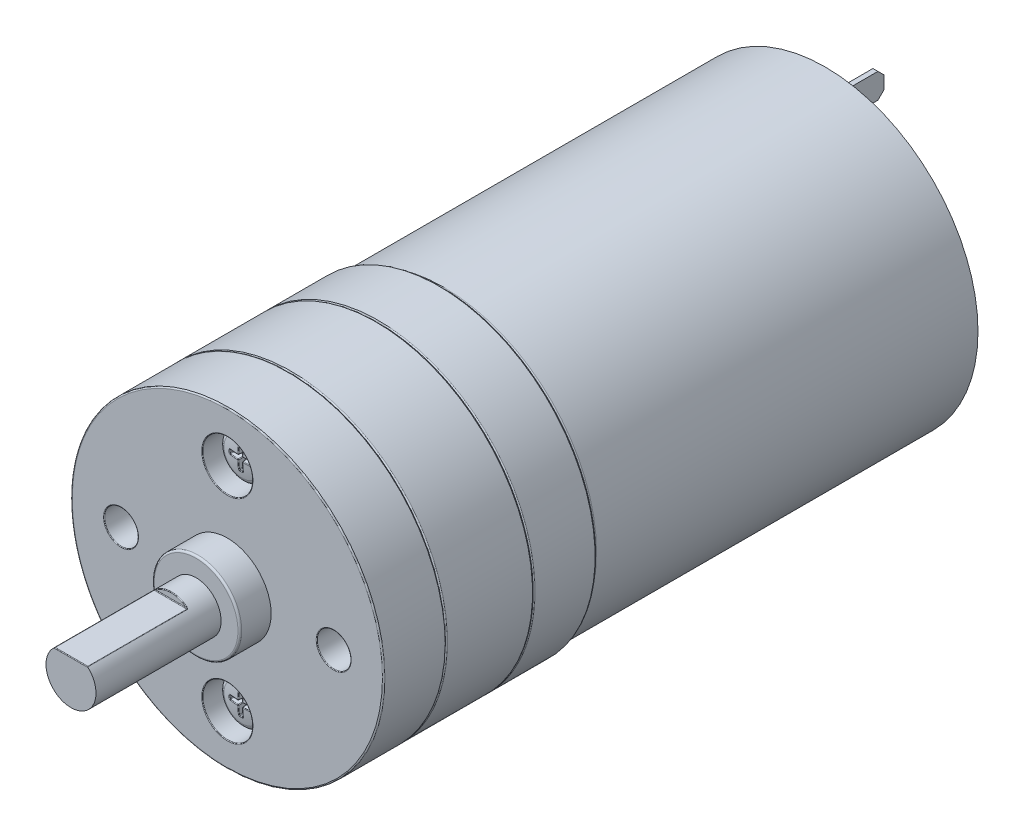
SolidWorks part; units mm, degrees
note: The reader was unsure of these and kept them because the rebuilt part matched: shared geometry of "Sketch8<3>".
material "Pololu 25D"
ref_plane "Front Plane" through (0, 0, 0) normal (0, 0, 1) x (1, 0, 0)
ref_plane "Top Plane" through (0, 0, 0) normal (0, 1, 0) x (1, 0, 0)
ref_plane "Right Plane" through (0, 0, 0) normal (1, 0, 0) x (0, 0, -1)
sketch "Sketch1" plane through (0, 0, 0) normal (0, 0, 1) x (1, 0, 0)
  line L0 (0, 14.2614) -> (0, -13.956) construction
  line L1 (-19.3981, 0) -> (18.454, 0) construction
  circle A0 centre (0, 0) radius 12.5
  dimension "D1" = 25
extrude "Boss-Extrude1" add sketch "Sketch1" along normal blind 5
fillet "Fillet1" radius 0.1 2 edges at (12.5, 0, 0) (12.5, 0, 5)
sketch "Sketch2" plane through (0, 0, 0) normal (0, 0, -1) x (-1, 0, 0)
  circle A0 centre (0, 0) radius 12.5 construction
  circle A1 centre (0, 0) radius 12.5
extrude "Boss-Extrude2" add sketch "Sketch2" along normal blind 7
fillet "Fillet2" radius 0.1 2 edges at (-12.5, 0, -7) (-12.5, 0, 0)
sketch "Sketch3" plane through (0, 0, -7) normal (0, 0, -1) x (-1, 0, 0)
  circle A0 centre (0, 0) radius 12.5 construction
  circle A1 centre (0, 0) radius 12.5
extrude "Boss-Extrude3" add sketch "Sketch3" along normal blind 5
fillet "Fillet3" radius 0.1 2 edges at (-12.5, 0, -7) (-12.5, 0, -12)
ref_plane "Plane1" through (0, 0, -12.01) normal (0, 0, -1) x (-1, 0, 0)
sketch "Sketch4" plane through (0, 0, -12.01) normal (0, 0, -1) x (-1, 0, 0)
  circle A0 centre (0, 0) radius 12.2
  dimension "D1" = 24.4
extrude "Boss-Extrude4" add sketch "Sketch4" along normal blind 30.8
fillet "Fillet5" radius 0.3 1 edges at (-12.2, 0, -12.01)
sketch "Sketch5" plane through (0, 0, 5) normal (0, 0, 1) x (1, 0, 0)
  circle A0 centre (0, 0) radius 2
  circle A1 centre (0, 0) radius 3.5
  dimension "D1" = 7
  dimension "D2" = 4
extrude "Boss-Extrude5" add sketch "Sketch5" along normal blind 2.5 separate body
fillet "Fillet6" radius 0.15 1 edges at (3.5, 0, 7.5)
sketch "Sketch6" plane through (0, 0, 5) normal (0, 0, 1) x (1, 0, 0)
  circle A0 centre (0, 0) radius 2
  dimension "D1" = 4
extrude "Boss-Extrude6" add sketch "Sketch6" along normal blind 12.5 separate body
sketch "Sketch7" plane through (0, 0, 17.5) normal (0, 0, 1) x (1, 0, 0)
  line L1 (-2.2202, 1.5) -> (2.3117, 1.5)
  line L2 (-2.2202, 1.5) -> (-2.2202, 2.2464)
  line L3 (-2.2202, 2.2464) -> (2.3117, 2.2464)
  line L4 (2.3117, 1.5) -> (2.3117, 2.2464)
  dimension "D1" = 1.5
extrude "Cut-Extrude1" cut sketch "Sketch7" against normal blind 8
fillet "Fillet7" radius 0.05 5 edges at (0, 2, 9.5) (-1.3229, 1.5, 13.5) (1.3229, 1.5, 13.5) (0, 1.5, 9.5) (0, 1.5, 17.5)
sketch "Sketch8" plane through (0, 0, 5) normal (0, 0, 1) x (1, 0, 0)
  line L0 (0, -13.5953) -> (0, 13.0364) construction
  line L1 (-16.2585, 0) -> (15.7653, 0) construction
  circle A0 centre (0, 8.5) radius 1.35
  circle A1 centre (0, 8.5) radius 2
  circle A2 centre (8.5, 0) radius 1.35
  circle A3 centre (0, -8.5) radius 1.35
  circle A4 centre (-8.5, 0) radius 1.35
  circle A5 centre (0, -8.5) radius 2
  dimension "D1" = 8.5
  dimension "D2" = 2.7
  dimension "D3" = 4
  dimension "D4" = 4
extrude "Cut-Extrude2" cut sketch "Sketch8" against normal blind 7.5 contours A0 | A4 | A3 | A2
extrude "Cut-Extrude3" cut sketch "Sketch8<3>" against normal blind 2.5 contours A5 A3 | A1
sketch "Sketch8<3>" plane through (0, 0, 5) normal (0, 0, 1) x (1, 0, 0) same geometry as "Sketch8"
fillet "Fillet8" radius 0.05 12 edges at (1.35, 8.5, 2.5) (1.35, 8.5, -2.5) (2, 8.5, 5) (2, 8.5, 2.5) (9.85, 0, 5) (9.85, 0, -2.5) (-7.15, 0, 5) (-7.15, 0, -2.5) (2, -8.5, 5) (2, -8.5, 2.5) (1.35, -8.5, 2.5) (1.35, -8.5, -2.5)
sketch "Sketch9" plane through (0, 0, 0) normal (1, 0, 0) x (0, 0, -1)
  line L0 (-21.5751, 0) -> (20.178, 0) construction
  line L1 (2.45, 8.5) -> (-6.5024, 8.5) construction
  line L2 (2.45, 7.15) -> (2.45, 9.85) construction
  line L3 (-2.5867, 9.7535) -> (2.2083, 9.7535)
  line L4 (2.2083, 9.7535) -> (2.2083, 8.5)
  line L5 (-3.3226, 10.3451) -> (-2.5867, 10.3451)
  line L6 (-2.5867, 10.3451) -> (-2.5867, 9.7535)
  line L7 (-3.9772, 8.5) -> (2.2083, 8.5)
  arc A0 (-3.8096, 9.9586) -> (-3.9772, 8.5) centre (2.45, 8.5) ccw
  arc A1 (-3.3226, 10.3451) -> (-3.8096, 9.9586) centre (-3.3226, 9.8451) ccw
  point P17 (2.2083, 8.5)
  point P18 (-3.7067, 10.3451)
  point P21 (-3.7067, 6.6549)
  dimension "D1" = 0.5
revolve "Revolve1" add sketch "Sketch9" angle 360 about L1
sketch "Sketch10" plane through (0, 0, 5) normal (0, 0, 1) x (1, 0, 0)
  line L1 (-1, 8.75) -> (-0.25, 8.75)
  line L2 (-1, 8.75) -> (-1, 8.25)
  line L3 (-1, 8.25) -> (-0.25, 8.25)
  line L4 (1, 8.75) -> (1, 8.25)
  line L7 (-0.25, 7.5) -> (0.25, 7.5)
  line L8 (-0.25, 7.5) -> (-0.25, 8.25)
  line L9 (-0.25, 9.5) -> (0.25, 9.5)
  line L10 (0.25, 7.5) -> (0.25, 8.25)
  line L14 (-0.25, 8.75) -> (-0.25, 9.5)
  line L18 (0.25, 8.75) -> (0.25, 9.5)
  line L19 (0.25, 8.25) -> (1, 8.25)
  line L20 (0.25, 8.75) -> (1, 8.75)
  point P0 (0, 8.5)
  point P5 (0, 8.5)
  dimension "D1" = 0.5
  dimension "D2" = 0.5
  dimension "D3" = 2
  dimension "D4" = 2
extrude "Cut-Extrude4" cut sketch "Sketch10" against normal blind 2 draft 5
fillet "Fillet9" radius 0.05 32 edges at (0.9049, 8.5, 3.9132) (0, 9.4049, 3.9132) (0, 7.5951, 3.9132) (-0.9049, 8.5, 3.9132) (-0.45, 8.575, 3) (-0.8649, 8.6149, 3.4557) (-0.5334, 8.6584, 3.9531) (0.8649, 8.6149, 3.4557) (0.45, 8.575, 3) (0.5334, 8.6584, 3.9531) (0.1176, 8.6176, 3.4866) (0.075, 8.95, 3) (0.1149, 9.3649, 3.4557) (0.1584, 9.0334, 3.9531) (0.1149, 7.6351, 3.4557) (0.075, 8.05, 3) (0.1584, 7.9666, 3.9531) (0.1176, 8.3824, 3.4866) (0.45, 8.425, 3) (0.8649, 8.3851, 3.4557) (0.5334, 8.3416, 3.9531) (-0.1149, 9.3649, 3.4557) (-0.075, 8.95, 3) (-0.1176, 8.6176, 3.4866) (-0.1584, 9.0334, 3.9531) (-0.075, 8.05, 3) (-0.1149, 7.6351, 3.4557) (-0.1584, 7.9666, 3.9531) (-0.8649, 8.3851, 3.4557) (-0.45, 8.425, 3) (-0.1176, 8.3824, 3.4866) (-0.5334, 8.3416, 3.9531)
pattern_circular "CirPattern9" count 2 over 360 about axis through (0, 0, 5) along (0, 0, -1) of bodies 112 110
sketch "Sketch12" plane through (0, 0, -42.81) normal (0, 0, -1) x (-1, 0, 0)
  circle A0 centre (0, 0) radius 0.75
  dimension "D1" = 1.5
extrude "Boss-Extrude7" [suppressed] add sketch "Sketch12" along normal blind 5
ref_plane "Plane2" [suppressed] through (0, 0, -44.31) normal (0, 0, -1) x (-1, 0, 0)
sketch "Sketch11" [suppressed] plane through (0, 0, -44.31) normal (0, 0, -1) x (-1, 0, 0)
  line L0 (-19.5341, 0) -> (16.6653, 0) construction
  line L1 (0, -13.7268) -> (0, 12.8062) construction
  circle A0 centre (0, 0) radius 11.5
  circle A1 centre (0, 0) radius 1.25
  circle A2 centre (-10, 0) radius 0.75
  circle A3 centre (10, 0) radius 0.75
  dimension "D1" = 23
  dimension "D2" = 2.5
  dimension "D3" = 1.5
  dimension "D4" = 10
extrude "Boss-Extrude8" [suppressed] add sketch "Sketch11" along normal blind 1.5 separate body
ref_plane "Plane3" [suppressed] through (10, 0, 0) normal (1, 0, 0) x (0, 0, -1)
sketch "Sketch13" [suppressed] plane through (10, 0, 0) normal (1, 0, 0) x (0, 0, -1)
  line L0 (47.8175, 0) -> (55.0658, 0) construction
  line L1 (47.9808, 0.463) -> (45.81, 0.463)
  line L2 (45.81, -11.5) -> (45.81, 11.5) construction
  line L3 (45.81, 0.463) -> (45.81, 1.2364)
  line L4 (47.9808, 0.463) -> (47.9808, 0)
  line L5 (47.9808, 0) -> (52.2107, 0)
  arc A0 (52.2107, 0) -> (45.81, 1.2364) centre (48.891, 0) ccw
revolve "Revolve2" [suppressed] add sketch "Sketch13" angle 360 about L0
pattern_circular "CirPattern10" [suppressed] count 2 over 360
sketch "Sketch14" [suppressed] plane through (0, 0, -47.81) normal (0, 0, -1) x (-1, 0, 0)
  circle A0 centre (0, 0) radius 7
  dimension "D1" = 14
extrude "Boss-Extrude9" [suppressed] add sketch "Sketch14" along normal blind 3 separate body
sketch "Sketch15" [suppressed] plane through (0, 0, -50.81) normal (0, 0, -1) x (-1, 0, 0)
  circle A0 centre (0, 0) radius 5
  dimension "D1" = 10
extrude "Boss-Extrude10" [suppressed] add sketch "Sketch15" along normal blind 1 separate body
sketch "Sketch16" [suppressed] plane through (0, 0, -45.81) normal (0, 0, -1) x (-1, 0, 0)
  line L0 (0, -1.0748) -> (0, 12.7053) construction
  line L2 (-3.1876, 9.114) -> (3.1876, 9.114)
  line L3 (-3.1876, 9.114) -> (-3.1876, 7.1212)
  line L4 (-3.1876, 7.1212) -> (3.1876, 7.1212)
  line L5 (3.1876, 9.114) -> (3.1876, 7.1212)
  line L6 (-3.1876, 9.114) -> (3.1876, 7.1212) construction
  line L7 (-3.1876, 7.1212) -> (3.1876, 9.114) construction
  point P3 (0, 8.1176)
extrude "Boss-Extrude11" [suppressed] add sketch "Sketch16" along normal blind 5 separate body
sketch "Sketch18" [suppressed] plane through (0, 0, -50.81) normal (0, 0, -1) x (-1, 0, 0)
  line L0 (-3.1876, 8.1176) -> (3.1876, 8.1176) construction
  line L2 (3.1876, 7.1212) -> (3.1876, 9.114) construction
  line L4 (-2.8627, 8.8076) -> (2.8627, 8.8076)
  line L5 (-2.8627, 8.8076) -> (-2.8627, 7.4276)
  line L6 (-2.8627, 7.4276) -> (2.8627, 7.4276)
  line L7 (2.8627, 8.8076) -> (2.8627, 7.4276)
  line L8 (-2.8627, 8.8076) -> (2.8627, 7.4276) construction
  line L9 (-2.8627, 7.4276) -> (2.8627, 8.8076) construction
  line L10 (-3.1876, 9.114) -> (3.1876, 9.114)
  line L11 (-3.1876, 9.114) -> (-3.1876, 7.1212)
  line L12 (-3.1876, 7.1212) -> (3.1876, 7.1212)
  line L13 (3.1876, 9.114) -> (3.1876, 7.1212)
  line L14 (-3.1876, 9.114) -> (3.1876, 7.1212) construction
  line L15 (-3.1876, 7.1212) -> (3.1876, 9.114) construction
  point P6 (0, 8.1176)
  point P11 (0, 8.1176)
extrude "Cut-Extrude5" [suppressed] cut sketch "Sketch18" against normal blind 2.5
fillet "Fillet10" [suppressed] radius 0.05
fillet "Fillet11" [suppressed] radius 0.05
fillet "Fillet12" [suppressed] radius 0.05
sketch "Sketch19" [suppressed] plane through (0, 0, -51.81) normal (0, 0, -1) x (-1, 0, 0)
  circle A0 centre (0, 0) radius 0.75
  dimension "D1" = 1.5
extrude "Boss-Extrude12" [suppressed] add sketch "Sketch19" along normal blind 0.5 separate body
sketch "Sketch20" plane through (0, 0, -42.81) normal (0, 0, -1) x (-1, 0, 0)
  circle A0 centre (0, 0) radius 11.9
  circle A2 centre (0, 0) radius 12.2 construction
  dimension "D1" = 0.3
extrude "Cut-Extrude6" cut sketch "Sketch20" against normal blind 0.7
sketch "Sketch21" plane through (0, 0, -42.11) normal (0, 0, -1) x (-1, 0, 0)
  circle A0 centre (0, 0) radius 3.125
  dimension "D1" = 6.25
extrude "Boss-Extrude13" add sketch "Sketch21" along normal blind 2
sketch "Sketch23" plane through (0, 0, -42.11) normal (0, 0, -1) x (-1, 0, 0)
  line L0 (-0.3231, 9.09) -> (2.4611, 8.793) construction
  line L1 (-0.1534, 10.681) -> (2.6308, 10.384)
  line L2 (-0.4928, 7.499) -> (2.2914, 7.202)
  line L3 (-2.5522, -8.8468) -> (0.232, -9.1437) construction
  line L4 (-2.3825, -7.2558) -> (0.4017, -7.5528)
  line L5 (-2.7219, -10.4377) -> (0.0623, -10.7347)
  arc A0 (-0.1534, 10.681) -> (-0.4928, 7.499) centre (-0.3231, 9.09) ccw
  arc A1 (2.2914, 7.202) -> (2.6308, 10.384) centre (2.4611, 8.793) ccw
  arc A2 (-2.3825, -7.2558) -> (-2.7219, -10.4377) centre (-2.5522, -8.8468) ccw
  arc A3 (0.0623, -10.7347) -> (0.4017, -7.5528) centre (0.232, -9.1437) ccw
  circle A4 centre (-6.0795, -7.9291) radius 1.205
  circle A5 centre (3.814, -9.1437) radius 1.205
  circle A6 centre (-3.9287, 9.09) radius 1.205
  circle A7 centre (5.9648, 7.8718) radius 1.205
  point P2 (1.069, 8.9415)
  point P7 (-1.1601, -8.9953)
  dimension "D2" = 1.6
  dimension "D1" = 2.8
extrude "Boss-Extrude14" add sketch "Sketch23" along normal blind 0.2
sketch "Sketch24" plane through (0, 0, -42.31) normal (0, 0, -1) x (-1, 0, 0)
  line L1 (-0.2, 10) -> (0.2, 10)
  line L2 (-0.2, 10) -> (-0.2, 8)
  line L3 (-0.2, 8) -> (0.2, 8)
  line L4 (0.2, 10) -> (0.2, 8)
  line L5 (-0.2, -8) -> (0.2, -8)
  line L6 (-0.2, -8) -> (-0.2, -10)
  line L7 (-0.2, -10) -> (0.2, -10)
  line L8 (0.2, -8) -> (0.2, -10)
  dimension "D1" = 0.4
  dimension "D2" = 2
  dimension "D3" = 0.2
  dimension "D4" = 8
  dimension "D5" = 8
extrude "Boss-Extrude15" add sketch "Sketch24" along normal blind 5
fillet "Fillet13" radius 0.5 1 edges at (-3.125, 0, -44.11)
chamfer "Chamfer1" distance 0.5 angle 45 4 edges at (0, -10, -47.31) (0, -8, -47.31) (0, 8, -47.31) (0, 10, -47.31)
